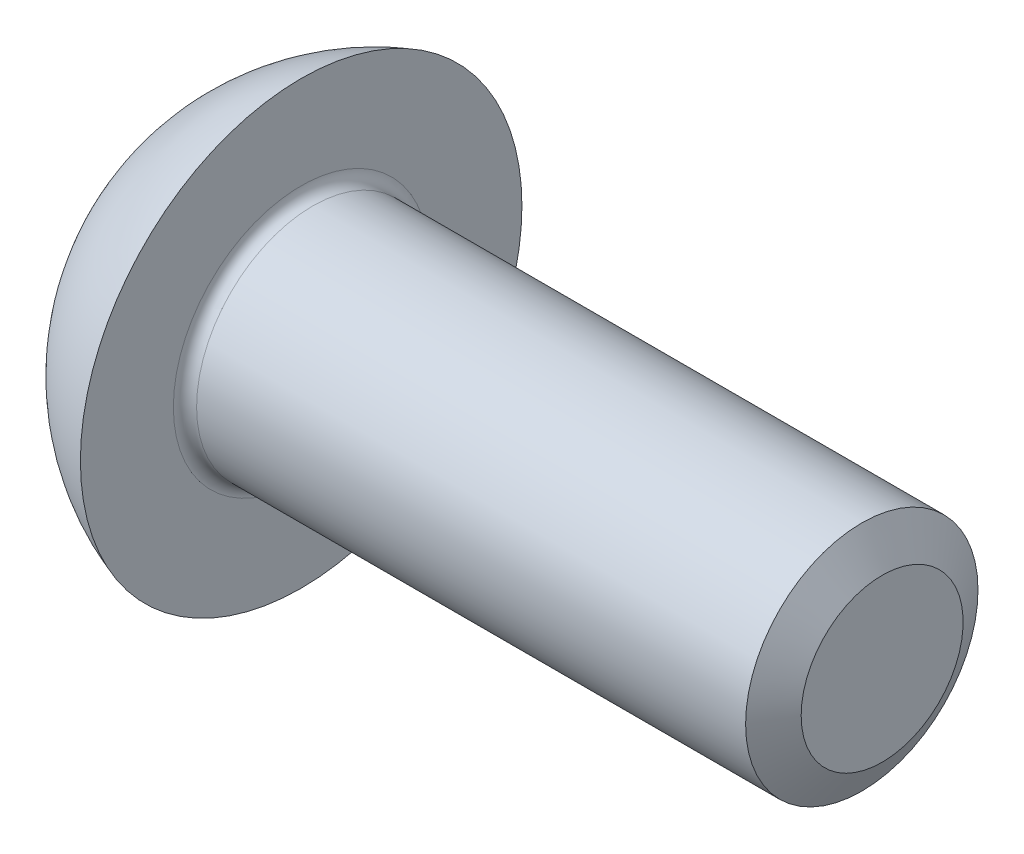
SolidWorks part; units mm, degrees
material "AISI 304"
ref_plane "前视基准面" through (0, 0, 0) normal (0, 0, 1) x (1, 0, 0)
ref_plane "上视基准面" through (0, 0, 0) normal (0, 1, 0) x (1, 0, 0)
ref_plane "右视基准面" through (0, 0, 0) normal (1, 0, 0) x (0, 0, -1)
sketch "尺寸草图" plane through (0, 0, 0) normal (0, 0, 1) x (1, 0, 0)
  line L0 (0, 0) -> (10, 0) construction
  line L1 (10, 0) -> (10, 2) construction
  line L2 (10, 2) -> (9.3, 2) construction
  line L3 (0, 0) -> (0, 3.8) construction
  point P3 (1.4, 0)
  point P6 (10, 2.35)
  point P7 (0, 0.93)
  point P9 (2.2, 0)
  point P10 (2.4, 0)
  point P11 (10, 1.25)
  point P12 (3.7, 0)
  point P13 (4, 0)
  point P14 (10, 12.35)
  dimension "l" = 10
  dimension "d" = 4
  dimension "P" = 0.7
  dimension "a" = 1.4
  dimension "da" = 4.7
  dimension "dk" = 7.6
  dimension "e" = 2.87
  dimension "K" = 2.2
  dimension "r" = 0.2
  dimension "s" = 2.5
  dimension "t" = 1.3
  dimension "w" = 0.3
  dimension "zslwx" = 10
sketch "草图1" plane through (0, 0, 0) normal (0, 0, 1) x (1, 0, 0)
  line L0 (-12.2, 0) -> (0, 0) construction
  line L1 (0, 2) -> (-9.8, 2)
  line L2 (-10, 2.2) -> (-10, 3.8)
  line L3 (-12.2, 0) -> (-12.2, 2)
  line L4 (0, 2) -> (0, 0)
  line L5 (-12.2, 0) -> (0, 0)
  arc A0 (-10, 3.8) -> (-12.2, 2) centre (-8.7273, 0) ccw
  arc A1 (-9.8, 2) -> (-10, 2.2) centre (-9.8, 2.2) cw
  point P10 (-10, 2)
  dimension "r" = 0.2
  dimension "d" = 4
  dimension "dk" = 7.6
  dimension "k" = 2.2
  dimension "l" = 10
revolve "旋转1" add sketch "草图1" angle 360 about L0
cosmetic thread "装饰螺纹线1" parameters "D1"=10, "D2"=3.44
sketch "草图2" plane through (-12.2, 0, 0) normal (-1, 0, 0) x (0, 0, 1)
  line L1 (0, 1.4434) -> (-1.25, 0.7217)
  line L2 (-1.25, 0.7217) -> (-1.25, -0.7217)
  line L3 (-1.25, -0.7217) -> (0, -1.4434)
  line L4 (0, -1.4434) -> (1.25, -0.7217)
  line L5 (1.25, -0.7217) -> (1.25, 0.7217)
  line L6 (1.25, 0.7217) -> (0, 1.4434)
  circle A0 centre (0, 0) radius 1.25 construction
  dimension "s" = 2.5
extrude "切除-拉伸1" cut sketch "草图2" against normal blind 2.2
sketch "草图6" plane through (0, 0, 0) normal (0, 0, 1) x (1, 0, 0)
  line L0 (-10.9, 1.4434) -> (-10, 0)
  line L1 (-9.63, 1.4434) -> (-9.63, 0)
  line L2 (-9.63, 1.4434) -> (-10.9, 1.4434)
  line L3 (-12.2, 0) -> (-10, 0) construction
  line L4 (-9.63, 0) -> (-10, 0)
  line L5 (-12.2, 0) -> (-15.07, 0) construction
  dimension "t" = 1.3
  dimension "e-s" = 0.37
  dimension "k" = 2.2
  dimension "e" = 2.87
revolve "旋转2" add sketch "草图6" angle 360 about L3
sketch "草图7" plane through (0, 0, 0) normal (0, 0, 1) x (1, 0, 0)
  line L3 (-12.2, 1.4434) -> (-11.83, 0)
  line L4 (-12.2, 0) -> (-11.83, 0) construction
  line L7 (-12.2, 1.4434) -> (-12.2, 0)
  line L8 (-12.2, 0) -> (-11.83, 0)
  dimension "e-s" = 0.37
revolve "切除-旋转5" cut sketch "草图7" angle 360 about L4
sketch "草图4" plane through (0, 0, 0) normal (0, 0, 1) x (1, 0, 0)
  line L0 (-0.35, 2) -> (0, 1.3938)
  line L1 (-0.35, 2) -> (0.35, 2)
  line L2 (0.35, 2) -> (0, 1.3938)
  line L4 (0, -2) -> (0, 2) construction
  line L5 (-0.35, 0) -> (0.35, 0) construction
  dimension "d" = 2
  dimension "p" = 0.7
revolve "切除-旋转1" cut sketch "草图4" angle 360 about L5
ref_axis "基准轴1" through (-8.1887, 0, 0) along (1, 0, 0)
pattern_linear "阵列(线性)1" [suppressed] count 12 spacing 0.7 along (-1, 0, 0) of bodies 104
